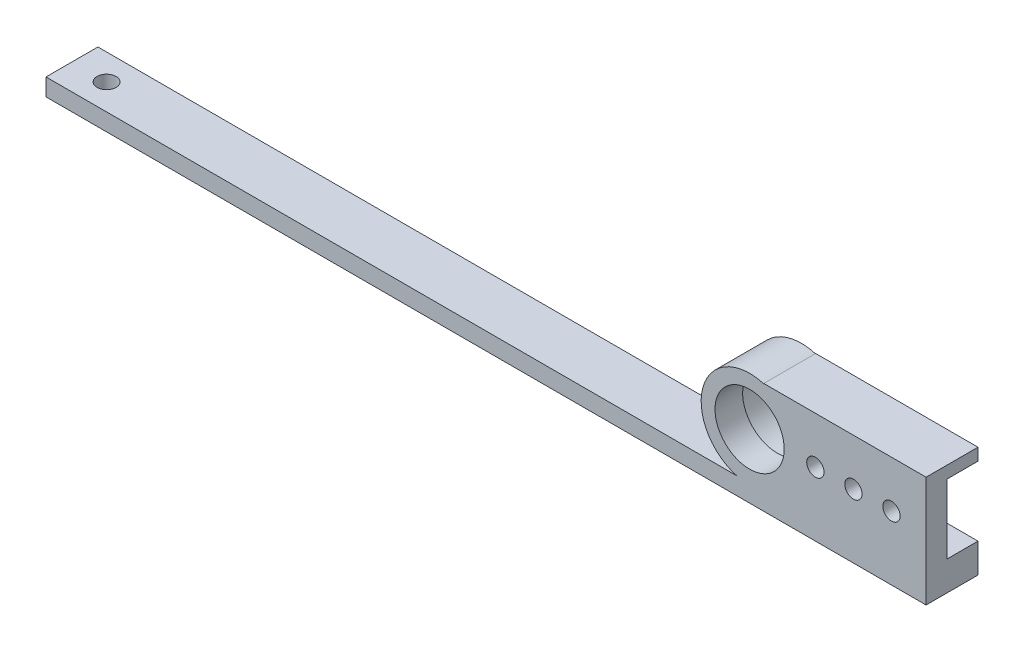
SolidWorks part; units mm, degrees
ref_plane "前视基准面" through (0, 0, 0) normal (0, 0, 1) x (1, 0, 0)
ref_plane "上视基准面" through (0, 0, 0) normal (0, 1, 0) x (1, 0, 0)
ref_plane "右视基准面" through (0, 0, 0) normal (1, 0, 0) x (0, 0, -1)
sketch "草图1" plane through (0, 0, 0) normal (0, 0, 1) x (1, 0, 0)
  line L1 (20, -10) -> (-20, -10)
  line L2 (20, -10) -> (20, 10)
  line L3 (20, 10) -> (-20, 10)
  line L4 (-20, -10) -> (-20, 10)
  line L5 (20, -10) -> (-20, 10) construction
  line L6 (20, 10) -> (-20, -10) construction
  point P0 (0, 0)
  dimension "D1" = 40
  dimension "D2" = 20
extrude "凸台-拉伸1" add sketch "草图1" along normal blind 6
sketch "草图2" plane through (0, 0, 6) normal (0, 0, 1) x (1, 0, 0)
  line L0 (20, -10) -> (20, 10) construction
  circle A0 centre (10, 0) radius 2.5
  circle A1 centre (-1, 0) radius 2.5
  circle A2 centre (-12, 0) radius 2.5
  dimension "D1" = 10
  dimension "D2" = 5
  dimension "D3" = 3
extrude "切除-拉伸1" cut sketch "草图2" against normal through all
sketch "草图3" plane through (0, 0, 6) normal (0, 0, 1) x (1, 0, 0)
  line L0 (20, 13.5) -> (20, 10)
  line L1 (20, -13.5) -> (-26.894, -13.5)
  line L3 (20, 13.5) -> (-26.894, 13.5)
  line L4 (-20, 10) -> (-20, -10)
  line L5 (-20, -10) -> (20, -10)
  line L6 (20, -10) -> (20, 10)
  line L7 (20, 10) -> (-20, 10)
  line L8 (-20, 10) -> (-20, -10)
  line L9 (-20, -10) -> (20, -10)
  line L10 (20, -10) -> (20, 10)
  line L11 (20, 10) -> (-20, 10)
  line L12 (-26.894, -13.5) -> (-26.894, 13.5)
  line L13 (20, -10.0394) -> (-26.894, 13.5) construction
  line L14 (20, 10.0394) -> (-26.894, -13.5) construction
  line L15 (20, -10) -> (20, -13.5)
  circle A0 centre (-31, 0) radius 11
  circle A1 centre (-31, 0) radius 14
  point P2 (0, 0)
  line M10 (-20, 10) -> (-20, -10)
  line M11 (-20, -10) -> (20, -10)
  line M13 (20, 10) -> (-20, 10)
  dimension "D3" = 22
  dimension "D4" = 28
  dimension "D2" = 3.5
  dimension "D1" = 0
extrude "凸台-拉伸2" add sketch "草图3" against normal blind 15 contours L3 A1 L1 L12 A0 | A1 L1 L15 M11 M10 | L1 A1 L8 A0 L12 | L8 A1 L3 L12 A0 | L8 A1 | A1 L0 L3 M10 M13 region at (-1.9449, 11.7771, 6) region at (-1.9449, -11.7771, 6) region at (-23.0173, 9.0328, 6) region at (-27.2274, 11.7946, 6) region at (-18.7882, 0, 6) region at (-23.0173, -9.0328, 6)
sketch "草图5" plane through (0, 0, 6) normal (0, 0, 1) x (1, 0, 0)
  circle A0 centre (-31, 0) radius 10
  circle A1 centre (-31, 0) radius 11 construction
  circle A2 centre (-31, 0) radius 11
  dimension "D1" = 20
extrude "凸台-拉伸3" add sketch "草图5" against normal blind 8
sketch "草图6" plane through (0, 0, 6) normal (0, 0, 1) x (1, 0, 0)
  circle A0 centre (-31, 0) radius 8.5
  circle A1 centre (-31, 0) radius 10 construction
  circle A2 centre (-31, 0) radius 10
  dimension "D1" = 17
sketch "草图8" plane through (0, 0, 6) normal (0, 0, 1) x (1, 0, 0)
  line L0 (20, -13.5) -> (20, 13.5) construction
  line L1 (20, -13.5) -> (-26.894, -13.5) construction
  line L2 (20, 13.5) -> (-26.894, 13.5) construction
  line L3 (20, -13.5) -> (20, 13.5)
  line L4 (20, -13.5) -> (-26.894, -13.5)
  line L5 (20, 13.5) -> (-26.894, 13.5)
  line L6 (-45, -14) -> (-26.894, -13.5)
  line L7 (-45, -14) -> (-239, -14)
  line L8 (-45, -14) -> (-45, 14)
  line L9 (-45, 14) -> (-239, 14)
  line L10 (-239, -14) -> (-239, 14)
  line L11 (-45, -14) -> (-239, 14) construction
  line L12 (-45, 14) -> (-239, -14) construction
  line L13 (-45, 14) -> (-26.894, 13.3843)
  line L14 (-12, 0) -> (-31, 0)
  arc A0 (-26.894, 13.3843) -> (-26.894, -13.3843) centre (-31, 0) ccw construction
  arc A1 (-26.894, 13.3843) -> (-26.894, -13.3843) centre (-31, 0) ccw
  point P6 (-142, 0)
  dimension "D1" = 28
  dimension "D2" = 194
  dimension "D3" = 14
sketch "草图9" plane through (0, -13.5, 0) normal (0, -1, 0) x (1, 0, 0)
  circle A0 centre (10.5344, 0) radius 5.2388
sketch "草图10" plane through (20, 0, 0) normal (1, 0, 0) x (0, 0, -1)
  line L1 (9, -13.5) -> (-6, -13.5)
  line L2 (9, -13.5) -> (9, -18.5)
  line L3 (9, -18.5) -> (-6, -18.5)
  line L4 (-6, -13.5) -> (-6, -18.5)
  dimension "D1" = 5
extrude "凸台-拉伸4" add sketch "草图10" against normal blind 500
sketch "草图11" plane through (0, 0, -9) normal (0, 0, -1) x (-1, 0, 0)
  line L1 (22.0371, -11.3638) -> (33.5283, -11.3638)
  line L2 (22.0371, -11.3638) -> (22.0371, -16.4864)
  line L3 (22.0371, -16.4864) -> (33.5283, -16.4864)
  line L4 (33.5283, -11.3638) -> (33.5283, -16.4864)
extrude "凸台-拉伸5" add sketch "草图11" against normal through all
sketch "草图12" plane through (0, -18.5, 0) normal (0, -1, 0) x (1, 0, 0)
  line L0 (-234.3163, -11.9161) -> (-234.3163, 6)
  line L1 (-234.3163, 118.5858) -> (-234.3163, -251.4142) construction
  line L2 (-234.3163, -11.9161) -> (-95.8824, -11.9161) construction
  line L3 (-480, 6) -> (20, 6) construction
sketch "草图13" plane through (0, -18.5, 0) normal (0, -1, 0) x (1, 0, 0)
  line L1 (-234.3163, -11.9161) -> (-490.0472, -11.9161)
  line L2 (-234.3163, -11.9161) -> (-234.3163, 14.9475)
  line L3 (-234.3163, 14.9475) -> (-490.0472, 14.9475)
  line L4 (-490.0472, -11.9161) -> (-490.0472, 14.9475)
extrude "切除-拉伸2" cut sketch "草图13" against normal through all
sketch "草图14" plane through (0, -18.5, 0) normal (0, -1, 0) x (1, 0, 0)
  line L0 (-224.3163, 6) -> (-224.3163, -9)
  line L1 (-45, 6) -> (-239, 6) construction
  line L2 (-234.3163, -9) -> (20, -9) construction
  line L3 (-234.3163, -11.9161) -> (-234.3163, 6) construction
  circle A0 centre (-224.3163, -1.5) radius 2.75
  dimension "D2" = 5.5
  dimension "D1" = 10
extrude "切除-拉伸3" cut sketch "草图14" against normal blind 10 contours A0
